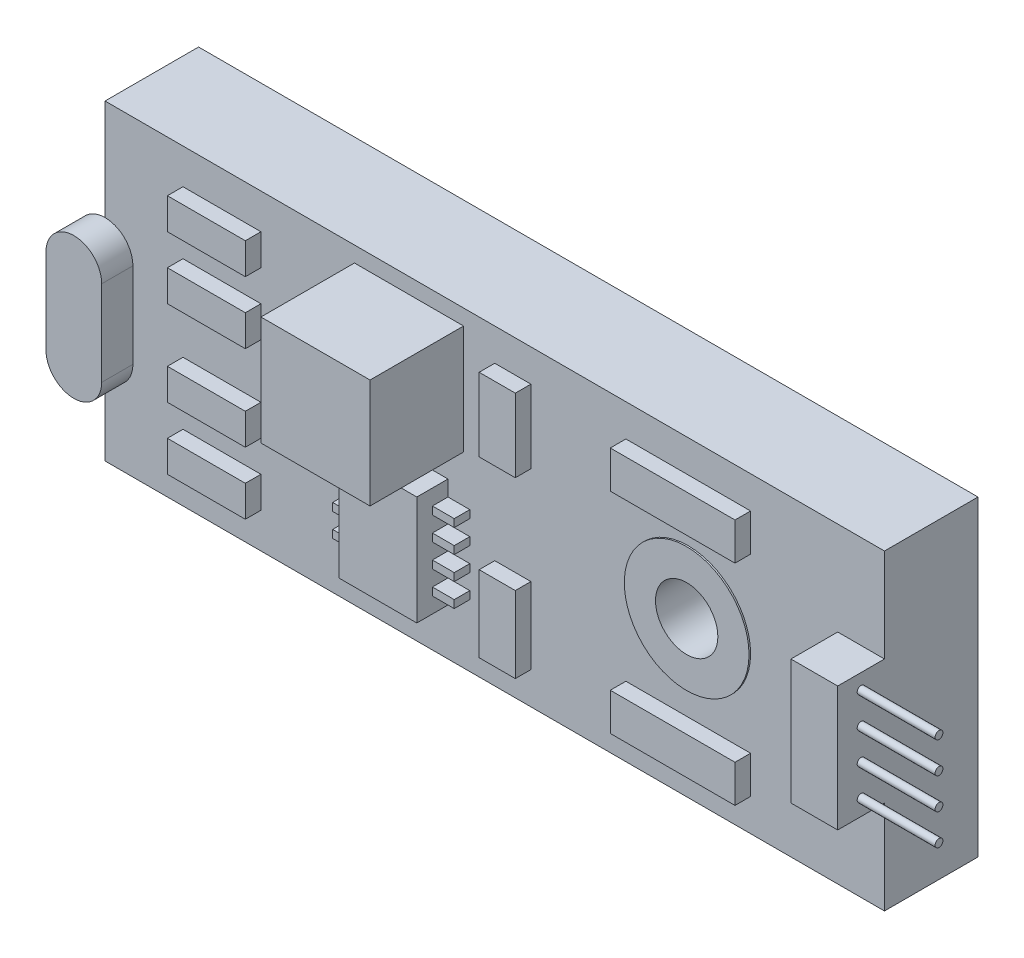
SolidWorks part; units mm, degrees
ref_plane "Alzado" through (0, 0, 0) normal (0, 0, 1) x (1, 0, 0)
ref_plane "Planta" through (0, 0, 0) normal (0, 1, 0) x (1, 0, 0)
ref_plane "Vista lateral" through (0, 0, 0) normal (1, 0, 0) x (0, 0, -1)
sketch "Croquis1" plane through (0, 0, 0) normal (0, 0, 1) x (1, 0, 0)
  line L1 (-12.5, -5) -> (12.5, -5)
  line L2 (-12.5, -5) -> (-12.5, 5)
  line L3 (-12.5, 5) -> (12.5, 5)
  line L4 (12.5, -5) -> (12.5, 5)
  line L5 (-12.5, -5) -> (12.5, 5) construction
  line L6 (-12.5, 5) -> (12.5, -5) construction
  point P0 (0, 0)
  dimension "D1" = 25
  dimension "D2" = 10
extrude "Saliente-Extruir1" add sketch "Croquis1" along normal blind 3
sketch "Croquis2" plane through (0, 0, 3) normal (0, 0, 1) x (1, 0, 0)
  circle A0 centre (6.2056, 0) radius 1
  circle A1 centre (6.2056, 0) radius 2
  dimension "D1" = 2
  dimension "D2" = 1
extrude "Cortar-Extruir1" cut sketch "Croquis2" against normal up to next contours A0
extrude "Saliente-Extruir2" add sketch "Croquis2<3>" against normal mid plane 0.1
sketch "Croquis2<3>" plane through (0, 0, 3) normal (0, 0, 1) x (1, 0, 0) same geometry as "Croquis2"
sketch "Croquis3" plane through (0, 0, 3) normal (0, 0, 1) x (1, 0, 0)
  line L1 (-1, 4.5) -> (-4.5, 4.5)
  line L2 (-1, 4.5) -> (-1, 1)
  line L3 (-1, 1) -> (-4.5, 1)
  line L4 (-4.5, 4.5) -> (-4.5, 1)
  dimension "D1" = 3.5
  dimension "D2" = 3.5
  dimension "D3" = 1
  dimension "D4" = 1
extrude "Saliente-Extruir3" add sketch "Croquis3" along normal blind 3
sketch "Croquis4" plane through (0, 0, 3) normal (0, 0, 1) x (1, 0, 0)
  line L0 (-4.5, 1) -> (-1, 1) construction
  line L1 (-4, 0) -> (-1.5, 0)
  line L2 (-4, 0) -> (-4, -3.5)
  line L3 (-4, -3.5) -> (-1.5, -3.5)
  line L4 (-1.5, 0) -> (-1.5, -3.5)
  dimension "D1" = 3.5
  dimension "D2" = 2.5
  dimension "D3" = 1.5
  dimension "D4" = 1
extrude "Saliente-Extruir4" add sketch "Croquis4" along normal blind 1
sketch "Croquis5" plane through (0, 0, 3) normal (0, 0, 1) x (1, 0, 0)
  line L14 (-4, 0) -> (-4, -3.5) construction
  line L15 (-4, -0.5) -> (-4.7, -0.5)
  line L16 (-4, -0.5) -> (-4, -0.75)
  line L17 (-4, -0.75) -> (-4.7, -0.75)
  line L18 (-4.7, -0.5) -> (-4.7, -0.75)
  line L19 (-4, 0) -> (-4, -3.5) construction
  line L20 (-4, -1.25) -> (-4.7, -1.25)
  line L21 (-4, -1.25) -> (-4, -1.5)
  line L22 (-4, -1.5) -> (-4.7, -1.5)
  line L23 (-4.7, -1.25) -> (-4.7, -1.5)
  line L24 (-4, -2) -> (-4.7, -2)
  line L25 (-4, -2) -> (-4, -2.25)
  line L26 (-4, -2.25) -> (-4.7, -2.25)
  line L27 (-4.7, -2) -> (-4.7, -2.25)
  line L28 (-4, -2.75) -> (-4.7, -2.75)
  line L29 (-4, -2.75) -> (-4, -3)
  line L30 (-4, -3) -> (-4.7, -3)
  line L31 (-4.7, -2.75) -> (-4.7, -3)
  line L32 (-1.5, 0) -> (-4, 0) construction
  line L33 (-2.75, 0) -> (-2.75, -3.5) construction
  line L34 (-4, -3.5) -> (-1.5, -3.5) construction
  line L35 (-0.8, -2.75) -> (-0.8, -3)
  line L36 (-1.5, -3) -> (-0.8, -3)
  line L37 (-1.5, -2.75) -> (-1.5, -3)
  line L38 (-1.5, -2.75) -> (-0.8, -2.75)
  line L39 (-0.8, -2) -> (-0.8, -2.25)
  line L40 (-1.5, -2.25) -> (-0.8, -2.25)
  line L41 (-1.5, -2) -> (-1.5, -2.25)
  line L42 (-1.5, -2) -> (-0.8, -2)
  line L43 (-0.8, -1.25) -> (-0.8, -1.5)
  line L44 (-1.5, -1.5) -> (-0.8, -1.5)
  line L45 (-1.5, -1.25) -> (-1.5, -1.5)
  line L46 (-1.5, -1.25) -> (-0.8, -1.25)
  line L47 (-0.8, -0.5) -> (-0.8, -0.75)
  line L48 (-1.5, -0.75) -> (-0.8, -0.75)
  line L49 (-1.5, -0.5) -> (-1.5, -0.75)
  line L50 (-1.5, -0.5) -> (-0.8, -0.5)
  dimension "D1" = 0.7
  dimension "D2" = 0.25
  dimension "D3" = 0.5
  dimension "D4" = 0.5
  dimension "D5" = 0.5
  dimension "D6" = 0.5
extrude "Saliente-Extruir5" add sketch "Croquis5" along normal blind 0.5
sketch "Croquis6" plane through (0, 0, 3) normal (0, 0, 1) x (1, 0, 0)
  line L0 (-12.5, 5) -> (-12.5, -5) construction
  line L1 (-10, 3.8687) -> (-7.5, 3.8687)
  line L2 (-10, 3.8687) -> (-10, 2.8687)
  line L3 (-10, 2.8687) -> (-7.5, 2.8687)
  line L4 (-7.5, 3.8687) -> (-7.5, 2.8687)
  line L5 (-10, 1.8687) -> (-7.5, 1.8687)
  line L6 (-10, 1.8687) -> (-10, 0.8687)
  line L7 (-10, 0.8687) -> (-7.5, 0.8687)
  line L8 (-7.5, 1.8687) -> (-7.5, 0.8687)
  line L9 (4.2056, -2.7649) -> (8.2056, -2.7649)
  line L10 (4.2056, -2.7649) -> (4.2056, -3.9649)
  line L11 (4.2056, -3.9649) -> (8.2056, -3.9649)
  line L12 (8.2056, -2.7649) -> (8.2056, -3.9649)
  dimension "D1" = 2.5
  dimension "D2" = 2.5
  dimension "D3" = 1
  dimension "D4" = 2.5
  dimension "D5" = 1
  dimension "D6" = 4
  dimension "D7" = 1.2
extrude "Saliente-Extruir6" add sketch "Croquis6" along normal blind 0.5
sketch "Croquis7" plane through (0, 0, 3) normal (0, 0, 1) x (1, 0, 0)
  line L1 (-12.5, 0) -> (0, 0) construction
  line L2 (-12.5, 5) -> (-12.5, -5) construction
  line L3 (-7.5, -1.8687) -> (-10, -1.8687)
  line L4 (-7.5, -0.8687) -> (-7.5, -1.8687)
  line L5 (4.2056, 0) -> (8.2056, 0) construction
  line L6 (8.2056, 2.7649) -> (4.2056, 2.7649)
  line L7 (8.2056, 3.9649) -> (8.2056, 2.7649)
  line L8 (4.2056, 3.9649) -> (8.2056, 3.9649)
  line L13 (4.2056, -2.7649) -> (4.2056, -3.9649)
  line L14 (4.2056, -3.9649) -> (8.2056, -3.9649)
  line L15 (8.2056, -3.9649) -> (8.2056, -2.7649)
  line L16 (8.2056, -2.7649) -> (4.2056, -2.7649)
  line L21 (-10, -0.8687) -> (-7.5, -0.8687)
  line L22 (-10, -1.8687) -> (-10, -0.8687)
  line L23 (-7.5, -3.8687) -> (-10, -3.8687)
  line L24 (-7.5, -2.8687) -> (-7.5, -3.8687)
  line L25 (-10, -2.8687) -> (-7.5, -2.8687)
  line L26 (-10, -3.8687) -> (-10, -2.8687)
  line L27 (4.2056, -2.7649) -> (4.2056, -3.9649)
  line L28 (4.2056, -3.9649) -> (8.2056, -3.9649)
  line L29 (8.2056, -3.9649) -> (8.2056, -2.7649)
  line L30 (8.2056, -2.7649) -> (4.2056, -2.7649)
  line L31 (4.2056, 2.7649) -> (4.2056, 3.9649)
  circle A0 centre (6.2056, 0) radius 2 construction
  circle A1 centre (6.2056, 0) radius 2 construction
  dimension "D1" = 0
extrude "Saliente-Extruir7" add sketch "Croquis7" along normal blind 0.5
sketch "Croquis8" plane through (0, 0, 3) normal (0, 0, 1) x (1, 0, 0)
  line L0 (12.5, -5) -> (12.5, 5) construction
  line L1 (12.5, 2) -> (11, 2)
  line L2 (12.5, 2) -> (12.5, -2)
  line L3 (12.5, -2) -> (11, -2)
  line L4 (11, 2) -> (11, -2)
  line L5 (12.5, 5) -> (-12.5, 5) construction
  dimension "D1" = 1.5
  dimension "D2" = 4
  dimension "D3" = 3
extrude "Saliente-Extruir8" add sketch "Croquis8" along normal blind 1.5 separate body
sketch "Croquis9" plane through (12.5, 0, 0) normal (1, 0, 0) x (0, 0, -1)
  line L0 (-3.75, 2) -> (-3.75, -2) construction
  line L1 (-4.5, 2) -> (-3, 2) construction
  line L2 (-4.5, -2) -> (-3, -2) construction
  circle A0 centre (-3.75, 1.5142) radius 0.125
  circle A1 centre (-3.75, 0.5142) radius 0.125
  circle A2 centre (-3.75, -0.4858) radius 0.125
  circle A3 centre (-3.75, -1.4858) radius 0.125
  dimension "D1" = 0.25
  dimension "D2" = 4
extrude "Saliente-Extruir9" add sketch "Croquis9" along normal blind 2.5
sketch "Croquis11" plane through (0, 0, 3) normal (0, 0, 1) x (1, 0, 0)
  line L0 (-12.5, 0.8687) -> (-12.5, -1.8687) construction
  line L1 (-12.5, 5) -> (-12.5, -5) construction
  line L2 (-11.6065, 0.8687) -> (-11.6065, -1.8687)
  line L3 (-13.3935, 0.8687) -> (-13.3935, -1.8687)
  arc A0 (-11.6065, 0.8687) -> (-13.3935, 0.8687) centre (-12.5, 0.8687) ccw
  arc A1 (-13.3935, -1.8687) -> (-11.6065, -1.8687) centre (-12.5, -1.8687) ccw
  point P4 (-12.5, -0.5)
extrude "Saliente-Extruir11" add sketch "Croquis11" along normal blind 1
sketch "Croquis12" plane through (0, 0, 3) normal (0, 0, 1) x (1, 0, 0)
  line L1 (0, 3.9649) -> (1.1592, 3.9649)
  line L2 (0, 3.9649) -> (0, 1.6137)
  line L3 (0, 1.6137) -> (1.1592, 1.6137)
  line L4 (1.1592, 3.9649) -> (1.1592, 1.6137)
  line L5 (0, -3.9649) -> (1.1592, -3.9649)
  line L6 (0, -3.9649) -> (0, -1.5188)
  line L7 (0, -1.5188) -> (1.1592, -1.5188)
  line L8 (1.1592, -3.9649) -> (1.1592, -1.5188)
extrude "Saliente-Extruir12" add sketch "Croquis12" along normal blind 0.5
